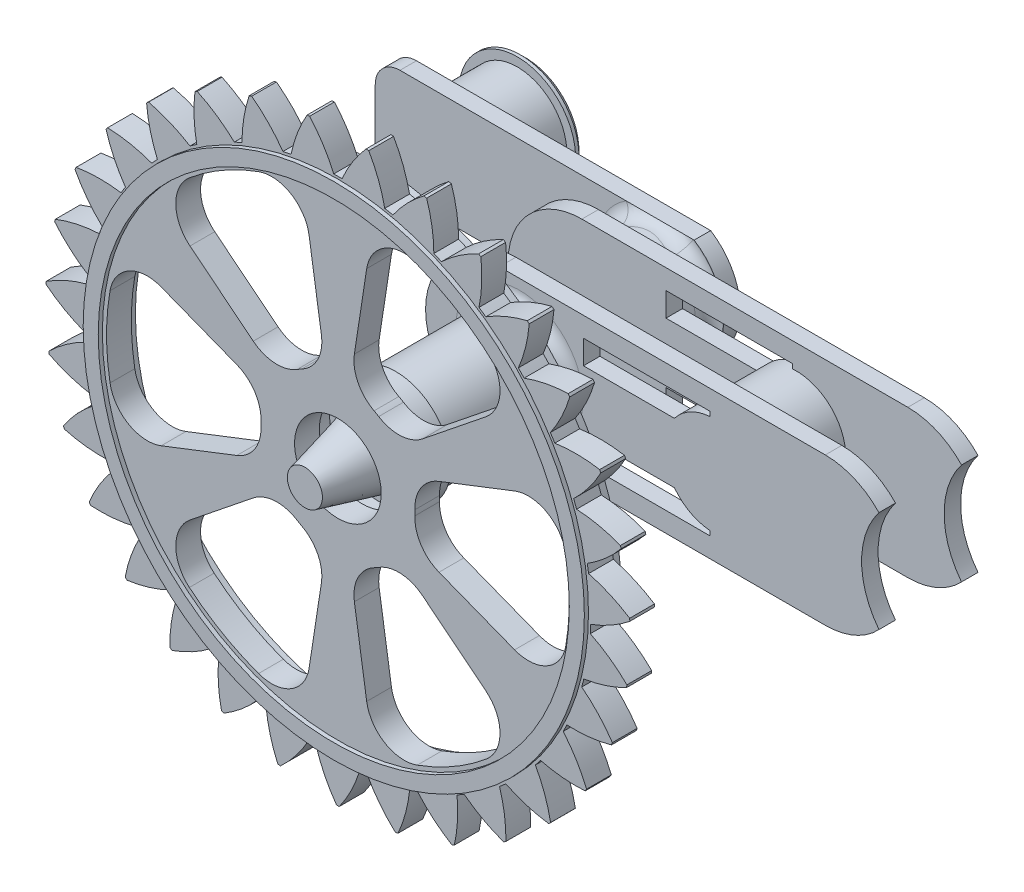
SolidWorks part; units mm, degrees
ref_plane "Plan de face" through (0, 0, 0) normal (0, 0, 1) x (1, 0, 0)
ref_plane "Plan de dessus" through (0, 0, 0) normal (0, 1, 0) x (1, 0, 0)
ref_plane "Plan de droite" through (0, 0, 0) normal (1, 0, 0) x (0, 0, -1)
sketch "Esquisse1" plane through (0, 0, 0) normal (0, 0, 1) x (1, 0, 0)
  line L0 (0, 0) -> (10.4221, 0) construction
  line L1 (10.4221, 0) -> (10.4221, 10.6188) construction
  line L2 (0.6982, 0.8941) -> (-3.2507, 0.8941)
  line L3 (-2.2321, -0.3641) -> (-0.6965, -0.3641)
  line L4 (-2.2321, 0.6536) -> (-0.6965, 0.6536)
  line L5 (0.6982, -0.8941) -> (-3.2507, -0.8941)
  line L6 (-2.2321, 0.6536) -> (-2.2321, 0.3641)
  line L7 (-2.2321, 0.3641) -> (-0.6965, 0.3641)
  line L8 (-0.6965, 0.6536) -> (-0.6965, 0.3641)
  line L9 (-0.6965, -0.6536) -> (-0.6965, -0.3641)
  line L10 (-2.2321, -0.6536) -> (-0.6965, -0.6536)
  line L11 (-2.2321, -0.6536) -> (-2.2321, -0.3641)
  circle A0 centre (0, 0) radius 0.6
  circle A1 centre (-3.0072, 0) radius 0.6
  arc A2 (-3.2507, 0.8941) -> (-3.2507, -0.8941) centre (-3.2507, 0) ccw
  arc A3 (0.6982, -0.8941) -> (1.3485, -0.6137) centre (0.6982, 0) ccw
  arc A4 (1.3485, 0.6137) -> (1.3485, -0.6137) centre (2.1379, 0) ccw
  arc A5 (1.3485, 0.6137) -> (0.6982, 0.8941) centre (0.6982, 0) ccw
extrude "Boss.-Extru.1" add sketch "Esquisse1" along normal blind 0.2 contours A1 | A0 | A4 A5 L2 A2 L5 A3 L10 L11 L3 L9 L4 L8 L7 L6 A0 A1 region at (-1.3303, 0, 0) region at (0, 0, 0) region at (-3.0072, 0, 0)
extrude "Boss.-Extru.2" add sketch "Esquisse1<3>" along normal blind 1.9 contours A1 region at (-3.0072, 0, 0)
sketch "Esquisse1<3>" plane through (0, 0, 0) normal (0, 0, 1) x (1, 0, 0) same geometry as "Esquisse1"
extrude "Boss.-Extru.3" add sketch "Esquisse1<4>" against normal blind 0.8 contours A0 region at (0, 0, 0)
sketch "Esquisse1<4>" plane through (0, 0, 0) normal (0, 0, 1) x (1, 0, 0) same geometry as "Esquisse1"
pattern_linear "Répétition linéaire1" count 2 spacing 1 along (0, 0, -1) of "Boss.-Extru.1"
sketch "Esquisse2" plane through (0, 0, -1) normal (0, 0, -1) x (-1, 0, 0)
  circle A0 centre (3.0072, 0) radius 0.6
extrude "Boss.-Extru.4" add sketch "Esquisse2" along normal blind 0.5
sketch "Esquisse3" plane through (0, 0, -1.5) normal (0, 0, -1) x (-1, 0, 0)
  line L1 (2.5907, 0.6536) -> (6.1548, 0.6536)
  line L3 (2.5906, -0.6535) -> (6.1548, -0.6535)
  line L4 (6.4548, 0.3536) -> (6.4548, -0.3535)
  circle A0 centre (5.5333, 0) radius 0.6
  arc A1 (6.1548, -0.6535) -> (6.4548, -0.3535) centre (6.1548, -0.3535) ccw
  arc A2 (6.4548, 0.3536) -> (6.1548, 0.6536) centre (6.1548, 0.3536) ccw
  arc A4 (2.5907, 0.6536) -> (2.5906, -0.6535) centre (3.0072, 0) ccw
  circle M1 centre (3.0072, 0) radius 0.6
  dimension "D1" = 0.3
extrude "Boss.-Extru.5" add sketch "Esquisse3" along normal blind 0.2 contours A0 | L1 A4 L3 A1 L4 A2 A0 M1 | M1 region at (-4.4617, 0.0001, -1.5) region at (-5.5333, 0, -1.5) region at (-3.0072, 0, -1.5)
extrude "Boss.-Extru.6" add sketch "Esquisse3<3>" along normal blind 0.8 contours A0 region at (-5.5333, 0, -1.5)
sketch "Esquisse3<3>" plane through (0, 0, -1.5) normal (0, 0, -1) x (-1, 0, 0) same geometry as "Esquisse3"
sketch "Esquisse4" plane through (0, 0, -2.3) normal (0, 0, -1) x (-1, 0, 0)
  circle A0 centre (5.5333, 0) radius 0.7062
extrude "Boss.-Extru.7" add sketch "Esquisse4" along normal blind 0.1
chamfer "Chanfrein1" distance 0.06 angle 45 1 edges at (-6.2396, 0, -2.4)
fillet "Congé1" radius 0.17 3 edges at (-3.6072, 0, -1.5) (-2.4072, 0, -1) (-2.4072, 0, 0.2)
sketch "Esquisse5" plane through (0, 0, 1.9) normal (0, 0, 1) x (1, 0, 0)
  circle A0 centre (-3.0072, 0) radius 0.6
  circle A1 centre (-3.0072, 0) radius 0.6679
extrude "Boss.-Extru.8" add sketch "Esquisse5" along normal blind 0.2 and the other way blind 0.2
sketch "Esquisse6" plane through (0, 0.8941, 0) normal (0, 1, 0) x (1, 0, 0)
  line L0 (1.3485, 0) -> (0.6982, 0) construction
  line L1 (-0.6, 0.8) -> (0.6982, 0.8)
  line L2 (-0.6, 0.8) -> (-0.6, 0)
  line L3 (-0.6, 0) -> (0.6982, 0)
  line L4 (0.6982, 0.8) -> (0.6982, 0)
extrude "Enlèv. mat.-Extru.1" cut sketch "Esquisse6" against normal blind 2.9
sketch "Esquisse7" plane through (0, 0, 0.2) normal (0, 0, 1) x (1, 0, 0)
  circle A0 centre (-0.6532, 0) radius 0.6
extrude "Boss.-Extru.9" add sketch "Esquisse7" against normal blind 1.1
sketch "Esquisse8" plane through (0, 0, 2.1) normal (0, 0, 1) x (1, 0, 0)
  line L0 (-3.0072, 0) -> (-3.0072, 6.7725) construction
  line L1 (-2.6583, 2.2708) -> (-2.8075, 1.2993)
  line L2 (-3.3561, 2.2708) -> (-3.2068, 1.2993)
  line L3 (-1.2151, 1.4376) -> (-1.9818, 0.8226)
  line L4 (-0.8661, 0.8332) -> (-1.7821, 0.4768)
  line L5 (-0.8661, -0.8332) -> (-1.7821, -0.4768)
  line L6 (-1.2151, -1.4376) -> (-1.9818, -0.8226)
  line L7 (-2.6583, -2.2708) -> (-2.8075, -1.2993)
  line L8 (-3.3561, -2.2708) -> (-3.2068, -1.2993)
  line L9 (-4.7993, -1.4376) -> (-4.0326, -0.8226)
  line L10 (-5.1483, -0.8332) -> (-4.2323, -0.4768)
  line L11 (-5.1483, 0.8332) -> (-4.2323, 0.4768)
  line L12 (-4.7993, 1.4376) -> (-4.0326, 0.8226)
  circle A0 centre (-3.0072, 0) radius 3.5405
  arc A1 (-3.9685, 2.6331) -> (-4.8068, 2.1491) centre (-3.0072, 0) ccw
  arc A2 (-3.4454, 0.8234) -> (-3.5012, 0.7912) centre (-3.0072, 0) ccw
  arc A4 (-3.2068, 1.2993) -> (-3.4454, 0.8234) centre (-3.6615, 1.2295) cw
  arc A5 (-2.8075, 1.2993) -> (-2.569, 0.8234) centre (-2.3529, 1.2295) ccw
  arc A6 (-2.0458, 2.6331) -> (-2.6583, 2.2708) centre (-2.2036, 2.201) ccw
  arc A7 (-3.3561, 2.2708) -> (-3.9685, 2.6331) centre (-3.8108, 2.201) ccw
  arc A8 (-0.2462, 0.484) -> (-0.8661, 0.8332) centre (-0.6993, 0.4046) ccw
  arc A9 (-1.2151, 1.4376) -> (-1.2076, 2.1491) centre (-1.5029, 1.7964) ccw
  arc A10 (-1.9818, 0.8226) -> (-2.5132, 0.7912) centre (-2.2696, 1.1814) cw
  arc A11 (-1.7821, 0.4768) -> (-2.075, 0.0322) centre (-1.6153, 0.0481) ccw
  arc A12 (-1.2076, -2.1491) -> (-1.2151, -1.4376) centre (-1.5029, -1.7964) ccw
  arc A13 (-0.8661, -0.8332) -> (-0.2462, -0.484) centre (-0.6993, -0.4046) ccw
  arc A14 (-1.7821, -0.4768) -> (-2.075, -0.0322) centre (-1.6153, -0.0481) cw
  arc A15 (-1.9818, -0.8226) -> (-2.5132, -0.7912) centre (-2.2696, -1.1814) ccw
  arc A16 (-3.9685, -2.6331) -> (-3.3561, -2.2708) centre (-3.8108, -2.201) ccw
  arc A17 (-2.6583, -2.2708) -> (-2.0458, -2.6331) centre (-2.2036, -2.201) ccw
  arc A18 (-2.8075, -1.2993) -> (-2.569, -0.8234) centre (-2.3529, -1.2295) cw
  arc A19 (-3.2068, -1.2993) -> (-3.4454, -0.8234) centre (-3.6615, -1.2295) ccw
  arc A20 (-5.7682, -0.484) -> (-5.1483, -0.8332) centre (-5.3151, -0.4046) ccw
  arc A21 (-4.7993, -1.4376) -> (-4.8068, -2.1491) centre (-4.5115, -1.7964) ccw
  arc A22 (-4.0326, -0.8226) -> (-3.5012, -0.7912) centre (-3.7448, -1.1814) cw
  arc A23 (-4.2323, -0.4768) -> (-3.9394, -0.0322) centre (-4.3991, -0.0481) ccw
  arc A24 (-4.8068, 2.1491) -> (-4.7993, 1.4376) centre (-4.5115, 1.7964) ccw
  arc A25 (-5.1483, 0.8332) -> (-5.7682, 0.484) centre (-5.3151, 0.4046) ccw
  arc A26 (-4.2323, 0.4768) -> (-3.9394, 0.0322) centre (-4.3991, 0.0481) cw
  arc A27 (-4.0326, 0.8226) -> (-3.5012, 0.7912) centre (-3.7448, 1.1814) ccw
  arc A28 (-5.7682, 0.484) -> (-5.7682, -0.484) centre (-3.0072, 0) ccw
  arc A29 (-4.8068, -2.1491) -> (-3.9685, -2.6331) centre (-3.0072, 0) ccw
  arc A30 (-2.0458, -2.6331) -> (-1.2076, -2.1491) centre (-3.0072, 0) ccw
  arc A31 (-0.2462, -0.484) -> (-0.2462, 0.484) centre (-3.0072, 0) ccw
  arc A32 (-1.2076, 2.1491) -> (-2.0458, 2.6331) centre (-3.0072, 0) ccw
  arc A33 (-3.9394, 0.0322) -> (-3.9394, -0.0322) centre (-3.0072, 0) ccw
  arc A34 (-2.5132, 0.7912) -> (-2.569, 0.8234) centre (-3.0072, 0) ccw
  arc A35 (-2.075, -0.0322) -> (-2.075, 0.0322) centre (-3.0072, 0) ccw
  arc A36 (-2.569, -0.8234) -> (-2.5132, -0.7912) centre (-3.0072, 0) ccw
  arc A37 (-3.5012, -0.7912) -> (-3.4454, -0.8234) centre (-3.0072, 0) ccw
  circle A38 centre (-3.0072, 0) radius 0.5249
  dimension "D1" = 0.46
extrude "Boss.-Extru.10" add sketch "Esquisse8" along normal blind 0.3
sketch "Esquisse9" plane through (0, 0, 2.4) normal (0, 0, 1) x (1, 0, 0)
  line L0 (-3.0072, 3.6601) -> (-3.0072, 5.3855) construction
  arc A0 (-2.5595, 3.6326) -> (-3.4549, 3.6326) centre (-3.0072, 0) ccw
  arc A1 (-2.9568, 3.0648) -> (-3.0575, 3.0648) centre (-3.0072, 0) ccw
  arc A2 (-2.5595, 3.6326) -> (-2.9568, 3.0648) centre (-1.3767, 2.3819) ccw
  arc A3 (-3.4549, 3.6326) -> (-3.0575, 3.0648) centre (-4.6377, 2.3819) cw
extrude "Enlèv. mat.-Extru.2" cut sketch "Esquisse9" against normal blind 0.3
pattern_circular "Répétition circulaire1" count 31 over 360 about axis through (-3.0072, 0, 2.4) along (0, 0, -1) of "Enlèv. mat.-Extru.2"
sketch "Esquisse10" plane through (0, 0, 2.1) normal (0, 0, -1) x (-1, 0, 0)
  circle A0 centre (3.0072, 0) radius 3.0362
  circle A1 centre (3.0072, 0) radius 2.8538
extrude "Boss.-Extru.11" add sketch "Esquisse10" along normal blind 0.1 and the other way blind 0.35
sketch "Esquisse11" plane through (0, 0, 2.1) normal (0, 0, -1) x (-1, 0, 0)
  circle A0 centre (3.0072, 0) radius 0.3873
extrude "Boss.-Extru.12" add sketch "Esquisse11" against normal blind 0.7 draft 14 separate body
